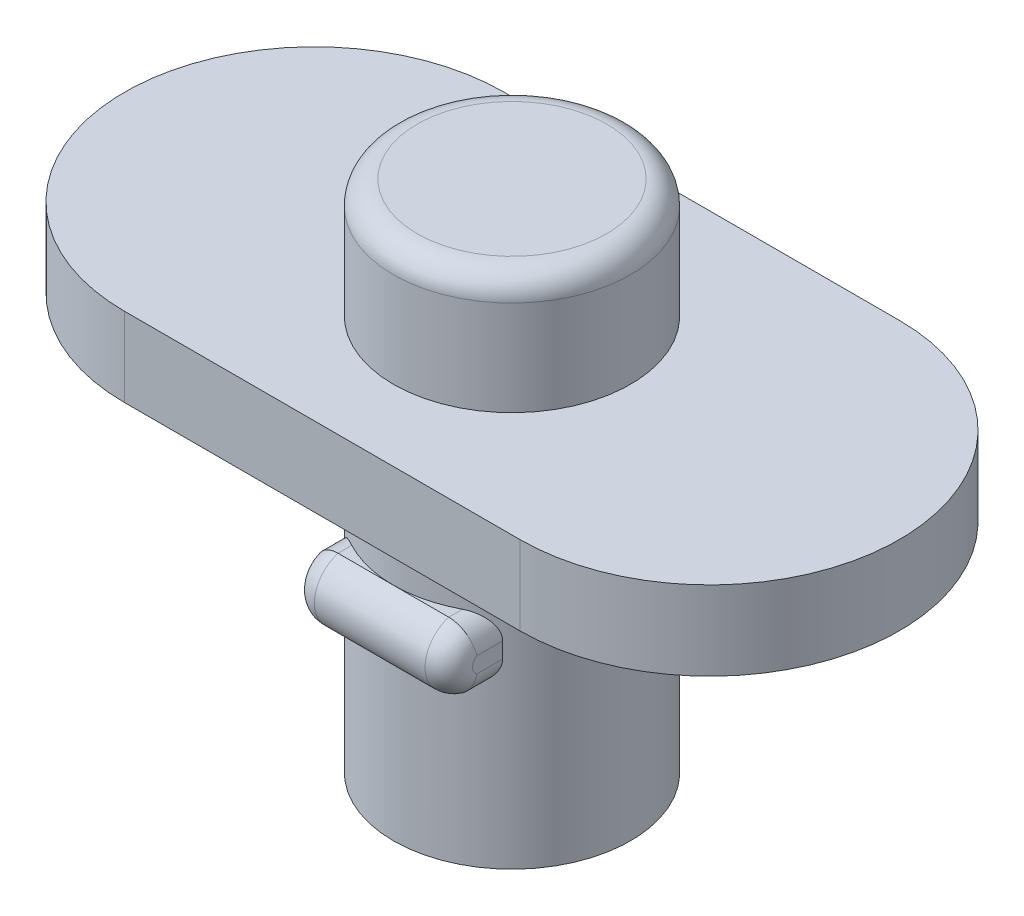
SolidWorks part; units mm, degrees
ref_plane "前视基准面" through (0, 0, 0) normal (0, 0, 1) x (1, 0, 0)
ref_plane "上视基准面" through (0, 0, 0) normal (0, 1, 0) x (1, 0, 0)
ref_plane "右视基准面" through (0, 0, 0) normal (1, 0, 0) x (0, 0, -1)
sketch "防尘基台草图" plane through (0, 0, 0) normal (0, 1, 0) x (1, 0, 0)
  line L16 (-2.5, -2.4) -> (2.5, -2.4)
  line L17 (-2.5, -2.4) -> (-2.5, 2.4) construction
  line L18 (-2.5, 2.4) -> (2.5, 2.4)
  line L19 (2.5, -2.4) -> (2.5, 2.4) construction
  line L20 (-2.5, -2.4) -> (2.5, 2.4) construction
  line L21 (-2.5, 2.4) -> (2.5, -2.4) construction
  arc A3 (-2.5, 2.4) -> (-2.5, -2.4) centre (-2.5, 0) ccw
  arc A4 (2.5, 2.4) -> (2.5, -2.4) centre (2.5, 0) cw
  point P0 (0, 0)
extrude "基台" add sketch "防尘基台草图" along normal blind 1 contours L16 A4 L18 A3
sketch "拨帽草图" plane through (0, 1, 0) normal (0, 1, 0) x (1, 0, 0)
  circle A0 centre (0, 0) radius 1.5
extrude "凸台-拉伸1" add sketch "拨帽草图" along normal blind 1.5
sketch "拨动开关连杆" plane through (0, 0, 0) normal (0, -1, 0) x (1, 0, 0)
  circle A0 centre (0, 0) radius 1.5
extrude "凸台-拉伸2" add sketch "拨动开关连杆" along normal blind 4
sketch "卡位草图" plane through (0, 0, 0) normal (0, 0, 1) x (1, 0, 0)
  line L0 (0, 0) -> (0, -1.6) construction
  line L1 (-1.5, 0) -> (1.5, 0) construction
  line L3 (-1, -2) -> (1, -2)
  line L4 (-1, -2) -> (-1, -1.2)
  line L5 (-1, -1.2) -> (1, -1.2)
  line L6 (1, -2) -> (1, -1.2)
  line L7 (-1, -2) -> (1, -1.2) construction
  line L8 (-1, -1.2) -> (1, -2) construction
extrude "凸台-拉伸3" add sketch "卡位草图" along normal blind 1.8 and the other way blind 1.8
sketch "草图4" plane through (1, 0, 0) normal (1, 0, 0) x (0, 0, -1)
  line L0 (0, 0) -> (0, -1.6)
  line L1 (1.8, -1.2) -> (1.118, -1.2) construction
  line L2 (-1.4, -2) -> (1.4, -2) construction
  line L3 (-1.4, -2) -> (-1.4, -1.2) construction
  line L4 (-1.4, -1.2) -> (1.4, -1.2) construction
  line L5 (1.4, -2) -> (1.4, -1.2) construction
  line L6 (-1.4, -1.6) -> (1.4, -1.6) construction
  line L7 (1.5, -1.2) -> (1.8, -1.2)
  line L9 (-1.8, -1.2) -> (-1.8, -2)
  line L12 (1.8, -1.2) -> (1.8, -2)
  line L14 (1.5, -2) -> (1.8, -2)
  line L15 (-1.8, -1.2) -> (-1.5, -1.2)
  line L16 (-1.8, -2) -> (-1.5, -2)
  arc A2 (-1.5, -2) -> (-1.5, -1.2) centre (-1.3833, -1.6) cw
  arc A3 (1.5, -1.2) -> (1.5, -2) centre (1.3833, -1.6) cw
  point P21 (0, -1.6)
  line M9 (-1.118, -1.2) -> (-1.8, -1.2)
  line M10 (-1.8, -1.2) -> (-1.8, -2)
  line M11 (-1.8, -2) -> (-1.118, -2)
extrude "切除-拉伸1" cut sketch "草图4" against normal blind 2 contours M9 M10 | L9 M11 | L12 | L12 region at (1, -1.9084, -1.7207) region at (1, -1.2916, -1.7207) region at (1, -1.2916, 1.7207) region at (1, -1.9084, 1.7207)
sketch "草图6" plane through (0, -4, 0) normal (0, -1, 0) x (1, 0, 0)
  line L9 (-0.85, -0.85) -> (0.85, -0.85)
  line L15 (-0.85, -0.85) -> (-0.85, 0.85)
  line L16 (-0.85, 0.85) -> (0.85, 0.85)
  line L17 (0.85, -0.85) -> (0.85, 0.85)
  line L18 (-0.85, -0.85) -> (0.85, 0.85) construction
  line L19 (-0.85, 0.85) -> (0.85, -0.85) construction
  point P0 (0, 0)
extrude "切除-拉伸2" cut sketch "草图6" against normal blind 2
fillet "圆角1" radius 0.3 13 edges at (0, 2.5, 1.5) (-1, -1.2, 1.309) (-1, -1.6, 1.8) (-1, -2, 1.309) (1, -2, 1.309) (1, -1.6, 1.8) (1, -1.2, 1.309) (-1, -1.2, -1.309) (-1, -1.6, -1.8) (-1, -2, -1.309) (1, -1.2, -1.309) (1, -2, -1.309) (1, -1.6, -1.8)
